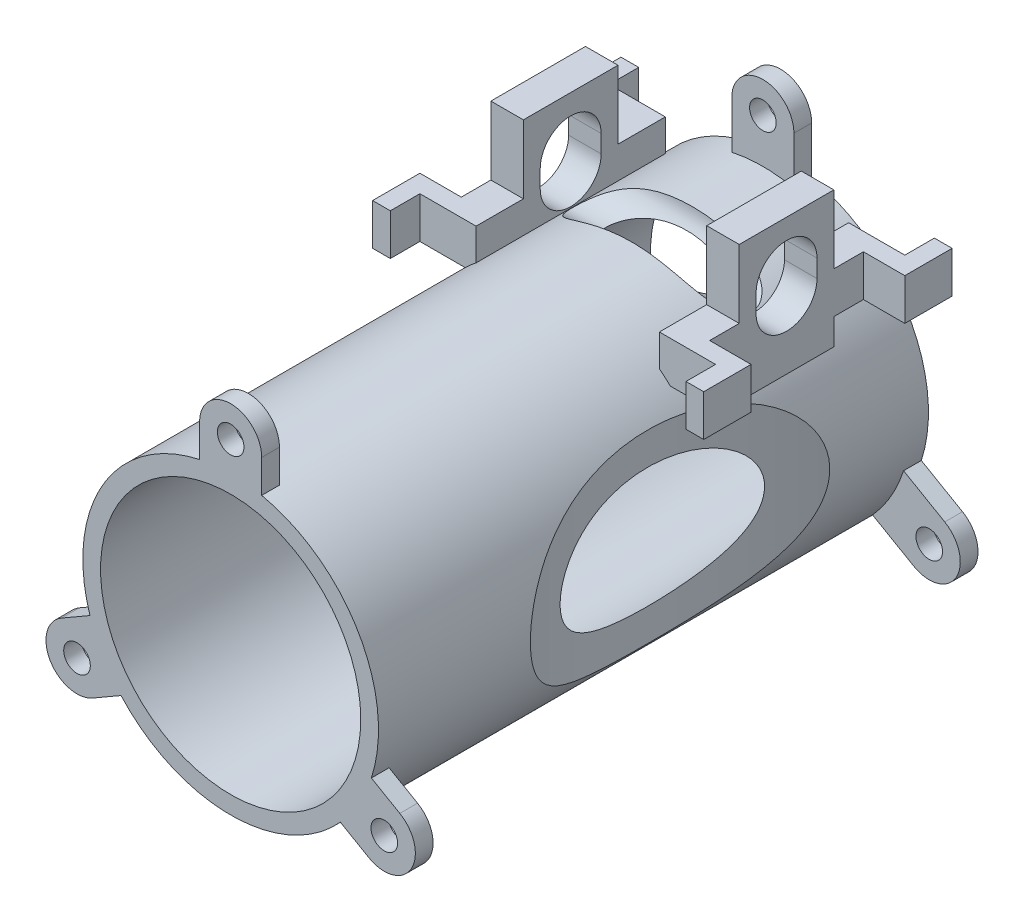
SolidWorks part; units mm, degrees
ref_plane "Front Plane" through (0, 0, 0) normal (0, 0, 1) x (1, 0, 0)
ref_plane "Top Plane" through (0, 0, 0) normal (0, 1, 0) x (1, 0, 0)
ref_plane "Right Plane" through (0, 0, 0) normal (1, 0, 0) x (0, 0, -1)
sketch "Sketch1" plane through (0, 0, 0) normal (0, 0, 1) x (1, 0, 0)
  circle A0 centre (0, 0) radius 22
  circle A1 centre (0, 0) radius 25
  dimension "D1" = 44
  dimension "D2" = 3
extrude "Boss-Extrude1" add sketch "Sketch1" along normal blind 40
ref_plane "Plane1" through (0, 0, 20) normal (0, 0, 1) x (1, 0, 0)
sketch "Sketch3" plane through (0, 0, 0) normal (1, 0, 0) x (0, 0, -1)
  line L0 (0, 25) -> (-40, 25) construction
  circle A0 centre (-20, 25) radius 5.15
  dimension "D1" = 10.3
extrude "Cut-Extrude1" cut sketch "Sketch3" against normal mid plane 50
sketch "Sketch7" plane through (0, 0, 40) normal (0, 0, 1) x (1, 0, 0)
  circle A0 centre (0, 0) radius 22
  circle A1 centre (0, 0) radius 25
extrude "Boss-Extrude4" add sketch "Sketch7" along normal blind 53
ref_plane "Plane2" through (-25, 0, 0) normal (-1, 0, 0) x (0, 0, 1)
sketch "Sketch9" plane through (0, 0, 0) normal (0, 0, -1) x (-1, 0, 0)
  line L0 (0, 0) -> (0, 32.4847) construction
  line L1 (-5.25, 32.4847) -> (-5.25, 24.4425)
  line L2 (5.25, 32.4847) -> (5.25, 24.4425)
  circle A0 centre (0, 32.4847) radius 2.25
  circle A1 centre (0, 32.4847) radius 5.25
  circle A2 centre (0, 0) radius 25 construction
  arc A3 (-5.25, 24.4425) -> (5.25, 24.4425) centre (0, 0) cw
  circle A6 centre (0, 32.4847) radius 2.25 construction
  circle M3 centre (0, 0) radius 25
  dimension "D1" = 4.5
  dimension "D2" = 3
extrude "Boss-Extrude5" add sketch "Sketch9" against normal blind 3 contours A1 L1 M3 | A1 A3 A0 M3 | A1 L2 M3 region at (0, 26.7779, 0) region at (0, 37.5862, 0)
pattern_circular "CirPattern1" count 3 over 360 about axis through (0, 0, 0) along (0, 0, 1) of "Boss-Extrude5"
sketch "Sketch10" plane through (0, 0, 93) normal (0, 0, 1) x (1, 0, 0)
  line L0 (-5.25, 30) -> (-5.25, 24.4425)
  line L1 (5.25, 30) -> (5.25, 24.4425)
  line L2 (0, 0) -> (0, 30) construction
  circle A0 centre (0, 30) radius 2.25
  circle A1 centre (0, 30) radius 5.25
  arc A2 (-5.25, 24.4425) -> (5.25, 24.4425) centre (0, 0) cw
  circle A3 centre (0, 0) radius 25 construction
  circle M5 centre (0, 0) radius 25
  dimension "D2" = 4.5
  dimension "D3" = 30
  dimension "D1" = 3
extrude "Boss-Extrude6" add sketch "Sketch10" against normal blind 3 contours A1 A0 M5 | A1 L0 M5 | A1 L1 M5 region at (-4.234, 25.9338, 93) region at (0, 35.103, 93) region at (4.234, 25.9338, 93)
pattern_circular "CirPattern2" count 3 every 120 about axis through (0, 0, 93) along (0, 0, 1) of "Boss-Extrude6"
ref_plane "Plane3" through (0, 11.51, 0) normal (0, 1, 0) x (1, 0, 0)
sketch "Sketch14" plane through (0, 0, 20) normal (0, 0, 1) x (1, 0, 0)
  line L0 (-21, 13.5647) -> (-21, 36.5647)
  line L1 (-21, 36.5647) -> (-15.5, 36.5647)
  line L2 (-15.5, 36.5647) -> (-15.5, 19.615)
  line L3 (-25, 27.5) -> (-25, -27.5) construction
  arc A0 (-5.25, 24.4425) -> (-23.7929, -7.6746) centre (0, 0) ccw construction
  arc A1 (-15.5, 19.615) -> (-21, 13.5647) centre (0, 0) ccw
  dimension "D1" = 23
  dimension "D2" = 4
  dimension "D3" = 5.5
extrude "Boss-Extrude7" add sketch "Sketch14" along normal mid plane 16
sketch "Sketch15" plane through (-21, 0, 0) normal (-1, 0, 0) x (0, 0, 1)
  line L0 (20, 25) -> (20, 28) construction
  line L1 (20, -27.5) -> (20, 27.5) construction
  line L2 (14.85, 25) -> (14.85, 28)
  line L3 (25.15, 25) -> (25.15, 28)
  line L4 (90, 25) -> (25.15, 25) construction
  arc A0 (14.85, 25) -> (25.15, 25) centre (20, 25) ccw
  arc A1 (25.15, 28) -> (14.85, 28) centre (20, 28) ccw
  point P4 (20, 26.5)
  dimension "D1" = 5.15
  dimension "D2" = 3
extrude "Cut-Extrude5" cut sketch "Sketch15" against normal blind 16
ref_plane "Plane5" through (0, 25, 0) normal (0, 1, 0) x (1, 0, 0)
sketch "Sketch17" plane through (0, 25, 0) normal (0, 1, 0) x (1, 0, 0)
  line L1 (-15.5, -28) -> (-21, -28)
  line L2 (-15.5, -28) -> (-15.5, -33)
  line L3 (-15.5, -33) -> (-21, -33)
  line L4 (-21, -28) -> (-21, -33)
  line L5 (-15.5, -28) -> (-21, -33) construction
  line L6 (-15.5, -33) -> (-21, -28) construction
  line L7 (-15.5, -33) -> (-28, -33)
  line L8 (-15.5, -33) -> (-15.5, -36)
  line L9 (-15.5, -36) -> (-28, -36)
  line L10 (-28, -33) -> (-28, -36)
  line L11 (-15.5, -33) -> (-28, -36) construction
  line L12 (-15.5, -36) -> (-28, -33) construction
  line L13 (-28, -36) -> (-25, -36)
  line L14 (-28, -36) -> (-28, -41)
  line L15 (-28, -41) -> (-25, -41)
  line L16 (-25, -36) -> (-25, -41)
  line L17 (-28, -36) -> (-25, -41) construction
  line L18 (-28, -41) -> (-25, -36) construction
  point P4 (-18.25, -30.5)
  point P10 (-21.75, -34.5)
  point P14 (-26.5, -38.5)
  dimension "D1" = 5
  dimension "D2" = 3
  dimension "D3" = 5
  dimension "D4" = 4
extrude "Boss-Extrude8" add sketch "Sketch17" against normal blind 7 contours L16 L9 L14 L15 | L7 L10 L9 L8 L3 | L1 L4 L3 L2 region at (-18.25, 25, 30.5) region at (-21.75, 25, 34.5) region at (-26.5, 25, 38.5)
mirror "Mirror1" about plane through (0, 0, 20) normal (0, 0, 1) of "Boss-Extrude8"
mirror "Mirror2" about plane through (0, 0, 0) normal (1, 0, 0) of "Mirror1", "Boss-Extrude8", "Cut-Extrude5", "Boss-Extrude7"
sketch "Sketch12" plane through (0, 11.51, 0) normal (0, 1, 0) x (1, 0, 0)
  line L0 (0, -44.5194) -> (0, -33.7673) construction
  line L1 (-25.5075, 0) -> (-33.3825, 0) construction
  circle A0 centre (-80.5, -42) radius 60
  circle A1 centre (80.5, -42) radius 60
  circle A2 centre (-80.5, -42) radius 61
  circle A3 centre (80.5, -42) radius 61
  dimension "D1" = 120
  dimension "D2" = 161
  dimension "D3" = 42
  dimension "D4" = 1
extrude "Cut-Extrude4" cut sketch "Sketch12" against normal blind 41 and the other way blind 6 contours A2 A0 | A1 | A3 A1 | A0 region at (80.5, 11.51, 42) region at (-141.3275, 11.51, 42) region at (19.6725, 11.51, 42)
